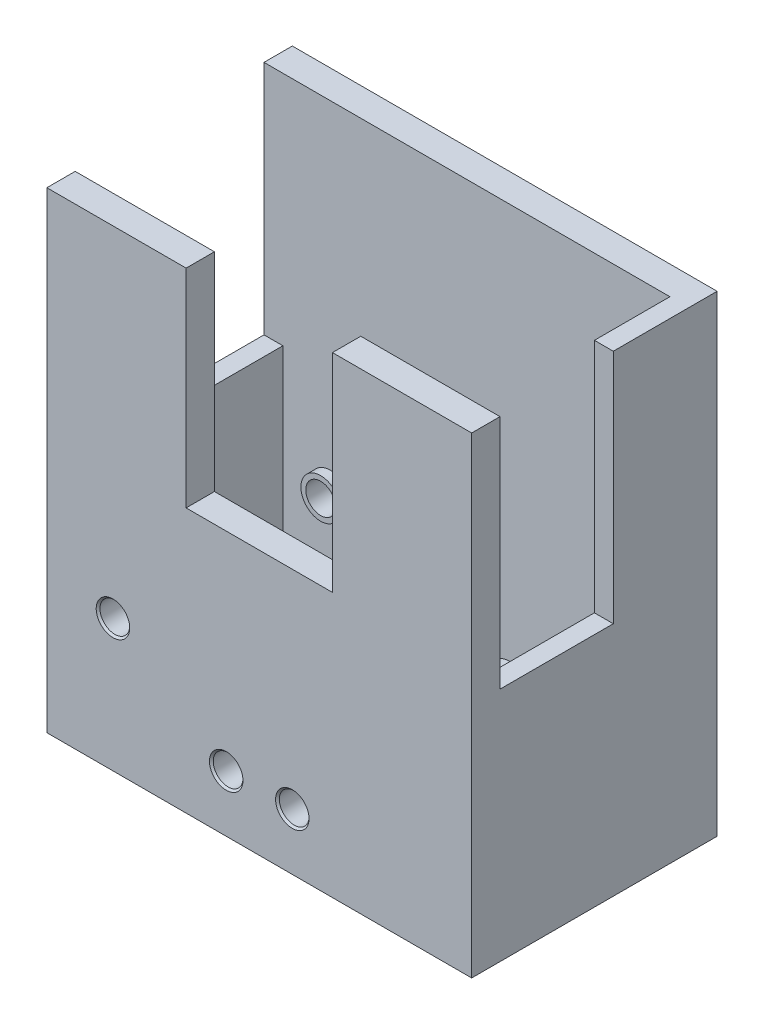
SolidWorks part; units mm, degrees
ref_plane "정면" through (0, 0, 0) normal (0, 0, 1) x (1, 0, 0)
ref_plane "윗면" through (0, 0, 0) normal (0, 1, 0) x (1, 0, 0)
ref_plane "우측면" through (0, 0, 0) normal (1, 0, 0) x (0, 0, -1)
sketch "스케치1" plane through (0, 0, 0) normal (0, 0, 1) x (1, 0, 0)
  line L1 (-20.5, 25) -> (20.5, 25)
  line L2 (-20.5, 25) -> (-20.5, -25)
  line L3 (-20.5, -25) -> (20.5, -25)
  line L4 (20.5, 25) -> (20.5, -25)
  line L5 (-20.5, 25) -> (20.5, -25) construction
  line L6 (-20.5, -25) -> (20.5, 25) construction
  point P0 (0, 0)
  dimension "D1" = 50
  dimension "D2" = 41
extrude "보스-돌출1" add sketch "스케치1" along normal blind 3
sketch "스케치3" plane through (0, 0, 3) normal (0, 0, 1) x (1, 0, 0)
  line L0 (20.5, 25) -> (-20.5, 25) construction
  line L1 (-7.75, 25) -> (7.75, 25)
  line L2 (-7.75, 25) -> (-7.75, 3)
  line L3 (-7.75, 3) -> (7.75, 3)
  line L4 (7.75, 25) -> (7.75, 3)
  line L5 (-20.5, 25) -> (-20.5, -25) construction
  dimension "D1" = 15.5
  dimension "D2" = 12.75
  dimension "D3" = 22
extrude "컷-돌출1" cut sketch "스케치3" against normal blind 18
sketch "스케치4" plane through (0, 0, 3) normal (0, 0, 1) x (1, 0, 0)
  line L0 (0, 3) -> (0, -25) construction
  line L1 (-7.75, 3) -> (7.75, 3) construction
  line L2 (-20.5, -25) -> (20.5, -25) construction
hole_wizard "M3.5 나사 구멍1" positions "스케치6" profile "스케치7" tap size "M3.5" standard "KS" end condition up to next
sketch "스케치6" plane through (0, 0, 3) normal (0, 0, 1) x (1, 0, 0)
  point P13 (-3.5, -19)
  point P15 (3.5, -19)
  point P23 (-15.5, -11)
cosmetic thread "구멍 나사산4" parameters "D2"=3.5
cosmetic thread "구멍 나사산5" parameters "D2"=3.5
cosmetic thread "구멍 나사산6" parameters "D2"=3.5
sketch "스케치7" plane through (-3.5, -19, 3) normal (1, 0, 0) x (0, -1, 0)
  line L0 (0, 0) -> (0, 3)
  line L1 (0, 3) -> (1.575, 3)
  line L2 (1.575, 3) -> (1.575, 0.2)
  line L3 (1.575, 0.2) -> (1.775, 0)
  line L5 (1.775, 0) -> (0, 0)
  line L6 (-1.575, 0.2) -> (-1.775, 0) construction
  line L11 (0, -6.35) -> (0, 107.95) construction
  dimension "관통 탭 드릴 지름" = 3.15
  dimension "관통 탭 드릴 깊이" = 3
  dimension "표면 카운터싱크 지름" = 3.55
  dimension "표면 카운터싱크 각도" = 90
sketch "스케치11" plane through (0, 25, 0) normal (0, 1, 0) x (1, 0, 0)
  line L0 (-7.75, 0) -> (-7.75, -3) construction
  line L1 (-7.75, -1.0286) -> (-20.05, -1.0286)
  line L2 (-7.75, -1.0286) -> (-7.75, -3)
  line L3 (-7.75, -3) -> (-20.05, -3)
  line L4 (-20.05, -1.0286) -> (-20.05, -3)
  line L5 (-7.75, -3) -> (-20.5, -3) construction
  dimension "D1" = 12.3
sketch "스케치16" plane through (0, 0, 0) normal (0, 0, -1) x (-1, 0, 0)
  line L0 (-20.5, -25) -> (-20.5, 25) construction
  line L1 (-20.5, -24.1279) -> (20.5, -24.1279)
  line L2 (-20.5, -24.1279) -> (-20.5, -25)
  line L3 (-20.5, -25) -> (20.5, -25)
  line L4 (20.5, -24.1279) -> (20.5, -25)
extrude "보스-돌출5" add sketch "스케치16" along normal blind 20
sketch "스케치17" plane through (0, 0, -20) normal (0, 0, -1) x (-1, 0, 0)
  line L1 (-20.5, 25) -> (20.5, 25)
  line L2 (-20.5, 25) -> (-20.5, -25)
  line L3 (-20.5, -25) -> (20.5, -25)
  line L4 (20.5, 25) -> (20.5, -25)
  circle A0 centre (15.5, -11) radius 1.575
  circle A1 centre (3.5, -19) radius 1.575
  circle A2 centre (-3.5, -19) radius 1.575
extrude "보스-돌출6" add sketch "스케치17" along normal blind 3 separate body
sketch "스케치20" plane through (20.5, 0, 0) normal (1, 0, 0) x (0, 0, -1)
  line L1 (-3, 25) -> (23, 25)
  line L2 (-3, 25) -> (-3, -25)
  line L3 (-3, -25) -> (23, -25)
  line L4 (23, 25) -> (23, -25)
extrude "보스-돌출8" add sketch "스케치20" along normal blind 2
sketch "스케치21" plane through (22.5, 0, 0) normal (1, 0, 0) x (0, 0, -1)
  line L0 (23, 25) -> (-3, 25) construction
  line L1 (0, 25) -> (12, 25)
  line L2 (0, 25) -> (0, 0)
  line L3 (0, 0) -> (12, 0)
  line L4 (12, 25) -> (12, 0)
  dimension "D1" = 12
  dimension "D2" = 25
extrude "컷-돌출2" cut sketch "스케치21" against normal blind 2
sketch "스케치22" plane through (-20.5, 0, 0) normal (-1, 0, 0) x (0, 0, 1)
  line L1 (-23, 25) -> (3, 25)
  line L2 (-23, 25) -> (-23, -25)
  line L3 (-23, -25) -> (3, -25)
  line L4 (3, 25) -> (3, -25)
extrude "보스-돌출9" add sketch "스케치22" along normal blind 2
sketch "스케치26" plane through (0, 25, 0) normal (0, 1, 0) x (1, 0, 0)
  line L0 (-20.5, 20) -> (-22.5, 20)
  line L1 (-22.5, -3) -> (-22.5, 23) construction
sketch "스케치27" plane through (-22.5, 0, 0) normal (-1, 0, 0) x (0, 0, 1)
  line L1 (-20, 25) -> (0, 25)
  line L2 (-20, 25) -> (-20, 0)
  line L3 (-20, 0) -> (0, 0)
  line L4 (0, 25) -> (0, 0)
  dimension "D1" = 25
extrude "컷-돌출3" cut sketch "스케치27" against normal blind 2
sketch "스케치9" plane through (0, 25, 0) normal (0, 1, 0) x (1, 0, 0)
hole_wizard "M3.5 나사 구멍2" positions "스케치33" profile "스케치34" tap size "M3.5" standard "KS"
sketch "스케치33" plane through (0, -24.1279, 0) normal (0, 1, 0) x (1, 0, 0)
  point P0 (-18.1614, 16.9005)
  point P2 (18.3097, 16.9005)
  point P4 (-18.1614, 2.9845)
  point P6 (18.3097, 2.9845)
sketch "스케치34" plane through (-18.1614, -24.1279, -16.9005) normal (1, 0, 0) x (0, 0, 1)
  line L0 (0, 0) -> (0, 10.8712)
  line L1 (0, 10.8712) -> (1.45, 10)
  line L2 (1.45, 10) -> (1.45, 0.325)
  line L3 (1.45, 0.325) -> (1.775, 0)
  line L5 (1.775, 0) -> (0, 0)
  line L6 (-1.45, 0.325) -> (-1.775, 0) construction
  line L10 (0, 10.8712) -> (-1.45, 10) construction
  line L11 (0, -6.35) -> (0, 107.95) construction
  dimension "탭 드릴 지름" = 2.9
  dimension "탭 드릴 깊이" = 10
  dimension "표면 카운터싱크 지름" = 3.55
  dimension "표면 카운터싱크 각도" = 90
  dimension "드릴 각도" = 118
cosmetic thread "구멍 나사산7" parameters "D1"=7, "D2"=3.5
cosmetic thread "구멍 나사산8" parameters "D1"=7, "D2"=3.5
cosmetic thread "구멍 나사산9" parameters "D1"=7, "D2"=3.5
cosmetic thread "구멍 나사산10" parameters "D1"=7, "D2"=3.5
sketch "스케치35" plane through (0, 0, -20) normal (0, 0, 1) x (1, 0, 0)
  point P0 (-15.5, -11)
  point P1 (-3.5, -19)
  point P3 (3.5, -19)
sketch "스케치36" plane through (0, 0, 0) normal (0, 0, -1) x (-1, 0, 0)
  circle A0 centre (-3.5, -19) radius 2.2183
  circle A1 centre (3.5, -19) radius 2.1816
  circle A2 centre (15.5, -11) radius 2.1646
  circle A3 centre (15.5, -10.8605) radius 1.7145
  circle A4 centre (3.5, -19) radius 1.575
  circle A5 centre (-3.5, -19) radius 1.575
extrude "보스-돌출10" add sketch "스케치36" along normal blind 1
sketch "스케치37" plane through (0, 0, -20) normal (0, 0, 1) x (1, 0, 0)
  circle A0 centre (-15.5, -11) radius 1.575
  circle A1 centre (-15.5, -11) radius 2.0945
  circle A2 centre (-3.5, -19) radius 1.575
  circle A3 centre (-3.5, -19) radius 1.9959
  circle A4 centre (3.5, -19) radius 1.575
  circle A5 centre (3.5, -19) radius 2.0642
extrude "보스-돌출11" add sketch "스케치37" along normal blind 1
sketch "스케치38" plane through (0, -24.1279, 0) normal (0, 1, 0) x (1, 0, 0)
  circle A0 centre (18.3097, 16.9005) radius 2.0072
  circle A1 centre (18.3097, 16.9005) radius 1.775
  circle A2 centre (18.3097, 2.9845) radius 1.775
  circle A3 centre (18.3097, 2.9845) radius 2.0522
  circle A4 centre (-18.1614, 16.9005) radius 1.775
  circle A5 centre (-18.1614, 16.9005) radius 2.1575
  circle A6 centre (-18.1614, 2.9845) radius 1.775
  circle A7 centre (-18.1614, 2.9845) radius 2.1321
extrude "보스-돌출12" add sketch "스케치38" along normal blind 0.5
